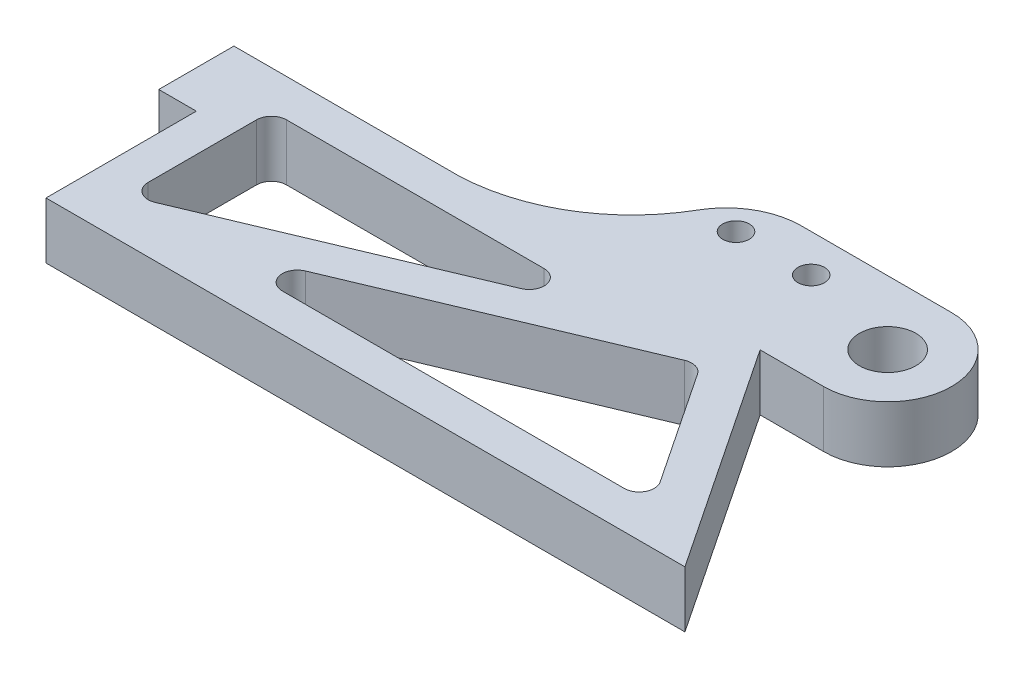
SolidWorks part; units mm, degrees
material "UHMW"
ref_plane "Front Plane" through (0, 0, 0) normal (0, 0, 1) x (1, 0, 0)
ref_plane "Top Plane" through (0, 0, 0) normal (0, 1, 0) x (1, 0, 0)
ref_plane "Right Plane" through (0, 0, 0) normal (1, 0, 0) x (0, 0, -1)
other "Bounding Box"
ref_plane "Default Plane" through (-8.9266, -12.7485, 0) normal (-0.1736, 0.9848, 0) x (0.9848, 0.1736, 0)
sketch "Sketch1" plane through (0, 0, 0) normal (0, 1, 0) x (1, 0, 0)
  line L0 (0, 0) -> (38.1, 0)
  line L1 (88.9, 0) -> (114.3, -38.1)
  line L2 (114.3, -38.1) -> (6.35, -38.1)
  line L3 (6.35, -38.1) -> (6.35, -12.7)
  line L4 (6.35, -12.7) -> (0, -12.7)
  line L5 (0, -12.7) -> (0, 0)
  line L6 (99.6289, 0) -> (88.9, 0)
  line L9 (99.6289, 21.632) -> (74.2289, 21.632)
  line L13 (85.9934, -7.0877) -> (102.4349, -31.75)
  line L14 (102.4349, -31.75) -> (27.3303, -31.75)
  line L15 (12.7, -31.0123) -> (12.7, -6.35)
  line L16 (12.7, -6.35) -> (71.363, -6.35)
  line L17 (12.7, -31.0123) -> (71.363, -6.35)
  line L18 (85.9934, -7.0877) -> (27.3303, -31.75)
  circle A0 centre (99.6289, 10.816) radius 4.7625
  arc A1 (99.6289, 21.632) -> (99.6289, 0) centre (99.6289, 10.816) cw
  arc A4 (74.2289, 21.632) -> (63.2185, 15.2614) centre (74.2289, 8.932) ccw
  arc A5 (63.2185, 15.2614) -> (38.1, 0) centre (36.7936, 30.452) cw
  circle A6 centre (69.5685, 15.2614) radius 2.2479
  circle A7 centre (82.2685, 15.2614) radius 2.2479
  point P16 (48.8289, 0)
  point P27 (83.3977, 17.3875)
  point P28 (72.4703, 15.8019)
  point P29 (71.6962, 15.2614)
  point P30 (0, 0)
  point P31 (0, 0)
  point P32 (0, 0)
  dimension "D7" = 50.8
  dimension "D8" = 9.525
  dimension "D9" = 10.7289
  dimension "D6" = 10.816
  dimension "D10" = 30.48
  dimension "D16" = 12.7
  dimension "D19" = 4.4958
  dimension "D1" = 6.35
  dimension "D2" = 38.1
  dimension "D3" = 107.95
  dimension "D4" = 88.9
  dimension "D5" = 12.7
  dimension "D11" = 6.35
  dimension "D12" = 6.35
  dimension "D13" = 6.35
  dimension "D14" = 6.35
  dimension "D15" = 6.35
  dimension "D17" = 38.1
  dimension "D18" = 25.4
  dimension "D20" = 6.35
  dimension "D21" = 12.7
extrude "Boss-Extrude1" add sketch "Sketch1" along normal blind 9.525
fillet "Fillet6" radius 2.54 6 edges at (102.4349, 4.7625, 31.75) (85.9934, 4.7625, 7.0877) (27.3303, 4.7625, 31.75) (12.7, 4.7625, 31.0123) (12.7, 4.7625, 6.35) (71.363, 4.7625, 6.35)
